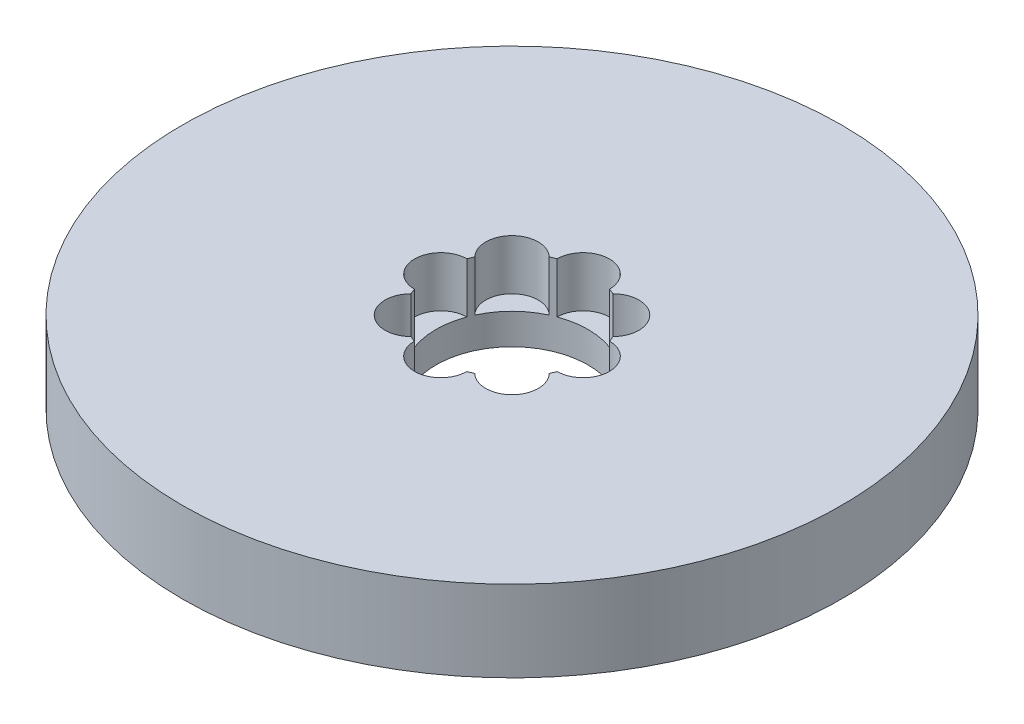
SolidWorks part; units mm, degrees
ref_plane "Front Plane" through (0, 0, 0) normal (0, 0, 1) x (1, 0, 0)
ref_plane "Top Plane" through (0, 0, 0) normal (0, 1, 0) x (1, 0, 0)
ref_plane "Right Plane" through (0, 0, 0) normal (1, 0, 0) x (0, 0, -1)
sketch "Sketch1" plane through (0, 0, 0) normal (0, 1, 0) x (1, 0, 0)
  circle A0 centre (0, 0) radius 65
  dimension "FLANGE_OD" = 130
extrude "Boss-Extrude1" add sketch "Sketch1" along normal blind 16
sketch "Sketch2" plane through (0, 0, 0) normal (0, 1, 0) x (1, 0, 0)
  circle A0 centre (0, 0) radius 15
  dimension "BORE_D" = 30
extrude "Cut-Extrude1" cut sketch "Sketch2" along normal through all
sketch "Sketch3" plane through (0, 16, 0) normal (0, 1, 0) x (1, 0, 0)
  circle A0 centre (0, 0) radius 14.0391 construction
  circle A1 centre (-14.0391, 0) radius 5.1798
  dimension "BOLT_D" = 10.3597
  dimension "BOLT_PCD" = 28.0782
extrude "Cut-Extrude2" cut sketch "Sketch3" against normal blind 9.9357
pattern_circular "CirPattern1" count 8 over 360 about axis through (0, 0, 0) along (0, 1, 0) of "Cut-Extrude2"
